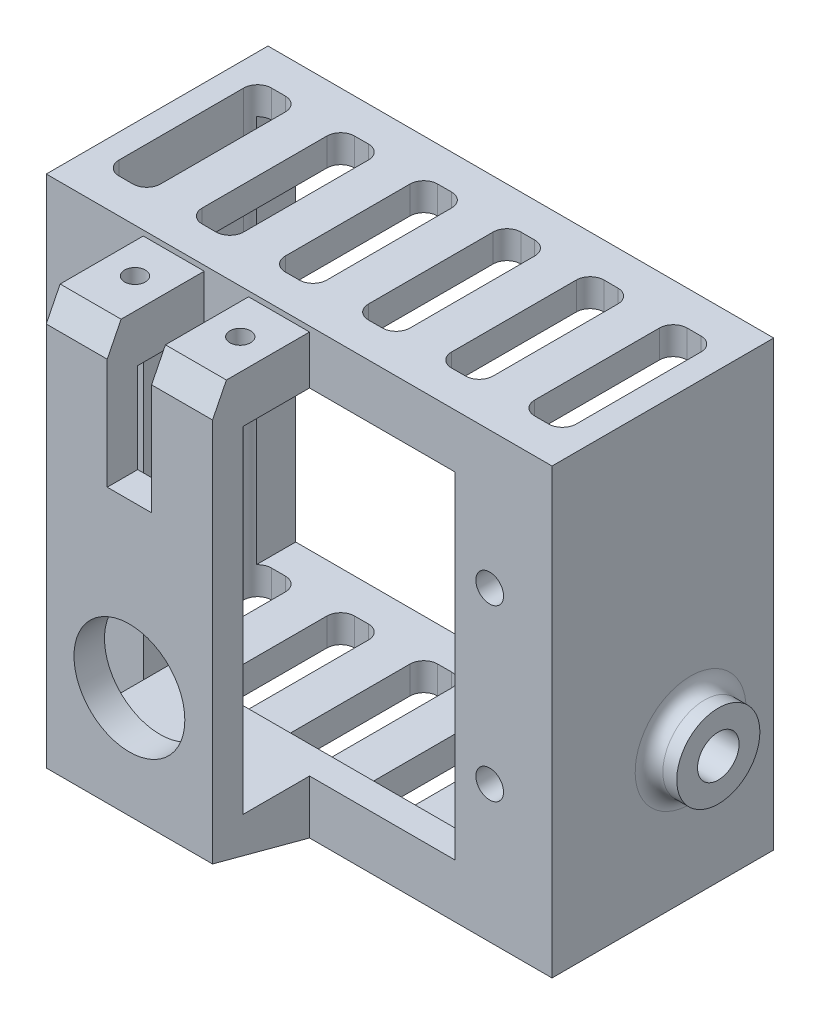
SolidWorks part; units mm, degrees
ref_plane "前视基准面" through (0, 0, 0) normal (0, 0, 1) x (1, 0, 0)
ref_plane "上视基准面" through (0, 0, 0) normal (0, 1, 0) x (1, 0, 0)
ref_plane "右视基准面" through (0, 0, 0) normal (1, 0, 0) x (0, 0, -1)
sketch "草图1" plane through (0, 0, 0) normal (0, 0, 1) x (1, 0, 0)
  line L0 (0, 16.832) -> (0, -37.7985) construction
  line L1 (-34.0238, 0) -> (58.9478, 0) construction
  line L2 (-19, 0) -> (-19, 8.7719) construction
  line L3 (8.5, 0) -> (8.5, 10.2817) construction
  line L4 (-19, 6) -> (8.5, 6) construction
  line L5 (-5.25, 8.9788) -> (-5.25, 6) construction
  line L6 (-16.5, 6) -> (-16.5, -18.25)
  line L7 (6, 6) -> (6, -18.25)
  line L9 (-16.5, 6) -> (6, 6)
  line L10 (-16.5, -18.25) -> (6, -18.25)
  line L11 (-21.5, 9.875) -> (11, 9.875)
  line L12 (11, 9.875) -> (11, -22.125)
  line L13 (-21.5, 9.875) -> (-21.5, -22.125)
  line L14 (-21.5, -22.125) -> (11, -22.125)
  line L15 (-16.5, -6.125) -> (6, -6.125) construction
  circle A0 centre (-19, 0) radius 1
  circle A1 centre (8.5, 0) radius 1
  circle A2 centre (-19, -12.25) radius 1
  circle A3 centre (8.5, -12.25) radius 1
  dimension "D3" = 2
  dimension "D1" = 6
  dimension "D2" = 24.25
  dimension "D4" = 16
  dimension "D5" = 16
  dimension "D6" = 8.5
  dimension "D7" = 16.5
  dimension "D8" = 5
  dimension "D9" = 5
  dimension "D10" = 6
extrude "凸台-拉伸1" add sketch "草图1" along normal blind 2
ref_plane "基准面4" through (0, 0, 9) normal (0, 0, 1) x (1, 0, 0)
sketch "草图2" plane through (0, 0, 9) normal (0, 0, 1) x (1, 0, 0)
  line L0 (-16.5, -6.125) -> (6, -6.125) construction
  line L1 (-16.5, 6) -> (-16.5, -18.25) construction
  line L2 (6, -18.25) -> (6, 6) construction
  line L3 (-5.25, 6) -> (-5.25, -18.25) construction
  line L4 (6, 6) -> (-16.5, 6) construction
  line L5 (-16.5, -18.25) -> (6, -18.25) construction
  line L6 (-19, -12.25) -> (8.5, -12.25) construction
  line L7 (-19, 0) -> (8.5, 0) construction
  line L9 (-4.5, -6.25) -> (-16.5, -6.25)
  line L10 (-4.5, -6.25) -> (-4.5, -18.25)
  line L11 (-4.5, -18.25) -> (-16.5, -18.25)
  line L12 (-16.5, -6.25) -> (-16.5, -18.25)
  line L13 (-4.5, -6.25) -> (-16.5, -18.25) construction
  line L14 (-4.5, -18.25) -> (-16.5, -6.25) construction
  circle A0 centre (-10.5, -12.25) radius 6 construction
  circle A2 centre (-10.5, -12.25) radius 4
  dimension "D2" = 12
  dimension "D3" = 8
  dimension "D1" = 19
  dimension "D4" = 12
extrude "凸台-拉伸2" add sketch "草图2" against normal blind 2.2 separate body
sketch "草图3" plane through (-16.5, 0, 0) normal (-1, 0, 0) x (0, 0, 1)
  line L0 (9, -18.25) -> (2, -18.25)
  line L1 (2, -18.25) -> (2, -22.125)
  line L2 (2, 9.875) -> (2, -22.125) construction
  line L3 (2, -22.125) -> (0, -22.125) construction
  line L4 (2, -22.125) -> (9, -20.25)
  line L5 (9, -20.25) -> (9, -18.25)
  dimension "D1" = 2
extrude "凸台-拉伸3" add sketch "草图3" against normal up to surface (12 mm away) up to face at (-4.5, -12.25, 7.9)
sketch "草图4" plane through (-16.5, 0, 0) normal (-1, 0, 0) x (0, 0, 1)
  line L0 (6.8, -6.25) -> (9, -6.25)
  line L1 (9, -6.25) -> (9, 9.5)
  line L2 (9, 9.5) -> (2, 9.5)
  line L3 (6.8, -6.25) -> (6.8, 6)
  line L4 (6.8, 6) -> (2, 6)
  line L5 (2, 6) -> (2, 9.5)
  dimension "D1" = 3.5
extrude "凸台-拉伸4" add sketch "草图4" against normal up to surface (12 mm away) up to face at (-4.5, -15.2292, 5.9333)
sketch "草图5" plane through (0, 0, 0) normal (0, 0, -1) x (-1, 0, 0)
  line L0 (-11, 9.875) -> (21.5, 9.875)
  line L1 (21.5, 9.875) -> (21.5, 7.875)
  line L2 (21.5, 9.875) -> (21.5, -22.125) construction
  line L3 (21.5, 7.875) -> (-11, 7.875)
  line L4 (-11, -22.125) -> (-11, 9.875) construction
  line L5 (-11, 7.875) -> (-11, 9.875)
  line L6 (-6, -6.125) -> (16.5, -6.125) construction
  line L7 (-6, -18.25) -> (-6, 6) construction
  line L8 (16.5, 6) -> (16.5, -18.25) construction
  line L9 (-11, -20.125) -> (-11, -22.125)
  line L10 (21.5, -20.125) -> (-11, -20.125)
  line L11 (21.5, -22.125) -> (21.5, -20.125)
  line L12 (-11, -22.125) -> (21.5, -22.125)
  dimension "D1" = 2
extrude "凸台-拉伸5" add sketch "草图5" along normal blind 14
sketch "草图7" plane through (0, 0, 2) normal (0, 0, 1) x (1, 0, 0)
  line L0 (-5.25, 9.875) -> (-5.25, 15.8183) construction
  line L1 (11, 9.875) -> (-21.5, 9.875) construction
  line L2 (-21.5, 9.875) -> (-23.5, 9.875)
  line L3 (-23.5, -22.125) -> (-21.5, -22.125)
  line L4 (-21.5, -22.125) -> (-21.5, 9.875)
  line L5 (-23.5, 9.875) -> (-23.5, -22.125)
  line L6 (13, 9.875) -> (13, -22.125)
  line L7 (11, -22.125) -> (11, 9.875)
  line L8 (13, -22.125) -> (11, -22.125)
  line L9 (11, 9.875) -> (13, 9.875)
  dimension "D1" = 2
extrude "凸台-拉伸6" add sketch "草图7" against normal blind 16
ref_plane "基准面5" through (0, 0, -8) normal (0, 0, -1) x (-1, 0, 0)
sketch "草图8" plane through (0, 0, -8) normal (0, 0, -1) x (-1, 0, 0)
  line L0 (-6, -6.125) -> (2.8741, -6.125) construction
  line L1 (-6, -18.25) -> (-6, 6) construction
  line L2 (19, -12.25) -> (-19.2584, -12.25) construction
  line L3 (19, -12.25) -> (28.1936, -12.25) construction
sketch "草图9" plane through (-23.5, 0, 0) normal (1, 0, 0) x (0, 0, -1)
  line L0 (8, -17.6) -> (8, 17.6) construction
  circle A0 centre (8, -12.25) radius 3.625
  dimension "D1" = 7.25
extrude "切除-拉伸1" cut sketch "草图9" along normal blind 1
sketch "草图10" plane through (-22.5, 0, 0) normal (-1, 0, 0) x (0, 0, 1)
  circle A0 centre (-8, -12.25) radius 2.25
  dimension "D1" = 4.5
extrude "切除-拉伸2" cut sketch "草图10" against normal blind 1
sketch "草图11" plane through (-23.5, 0, 0) normal (1, 0, 0) x (0, 0, -1)
  circle A0 centre (8, -12.25) radius 5
  circle A1 centre (8, -12.25) radius 3.625 construction
  circle A2 centre (8, -12.25) radius 3.625
  dimension "D1" = 10
extrude "凸台-拉伸7" add sketch "草图11" against normal blind 2
fillet "圆角1" radius 1 1 edges at (-23.5, -17.25, -8)
sketch "草图12" plane through (13, 0, 0) normal (-1, 0, 0) x (0, 0, 1)
  circle A0 centre (-8, -12.25) radius 1.5
  circle A1 centre (-8, -12.25) radius 3
  dimension "D1" = 3
  dimension "D2" = 6
extrude "凸台-拉伸8" add sketch "草图12" against normal blind 2
fillet "圆角2" radius 1 1 edges at (13, -9.25, -8)
sketch "草图13" plane through (13, 0, 0) normal (-1, 0, 0) x (0, 0, 1)
  circle A0 centre (-8, -12.25) radius 1.5 construction
  circle A1 centre (-8, -12.25) radius 1.5
extrude "切除-拉伸3" cut sketch "草图13" along normal blind 2
sketch "草图14" [suppressed] plane through (13, 0, 0) normal (1, 0, 0) x (0, 0, -1)
  circle A0 centre (8, -12.25) radius 3.625
  dimension "D1" = 7.25
extrude "切除-拉伸4" [suppressed] cut sketch "草图14" against normal blind 1
sketch "草图15" [suppressed] plane through (12, 0, 0) normal (1, 0, 0) x (0, 0, -1)
  circle A0 centre (8, -12.25) radius 2.25
  dimension "D1" = 4.5
extrude "切除-拉伸5" [suppressed] cut sketch "草图15" against normal blind 1
sketch "草图16" [suppressed] plane through (13, 0, 0) normal (1, 0, 0) x (0, 0, -1)
  circle A0 centre (8, -12.25) radius 5
  circle A1 centre (8, -12.25) radius 3.625 construction
  circle A2 centre (8, -12.25) radius 3.625
  dimension "D1" = 10
extrude "凸台-拉伸9" [suppressed] add sketch "草图16" along normal blind 2
fillet "圆角3" [suppressed] radius 1
sketch "草图17" [suppressed] plane through (-23.5, 0, 0) normal (-1, 0, 0) x (0, 0, 1)
  circle A0 centre (-8, -12.25) radius 1.5
  circle A1 centre (-8, -12.25) radius 3
  dimension "D1" = 3
  dimension "D2" = 6
extrude "凸台-拉伸10" [suppressed] add sketch "草图17" along normal blind 2
fillet "圆角4" [suppressed] radius 1
sketch "草图18" [suppressed] plane through (-23.5, 0, 0) normal (-1, 0, 0) x (0, 0, 1)
  circle A3 centre (-8, -12.25) radius 1.5
  circle A4 centre (-8, -12.25) radius 1.5
  dimension "D1" = 0
extrude "切除-拉伸6" [suppressed] cut sketch "草图18" against normal blind 2
sketch "草图19" plane through (0, 9.5, 0) normal (0, 1, 0) x (1, 0, 0)
  line L0 (-10.5, -9) -> (-10.5, -2) construction
  line L1 (-4.5, -9) -> (-16.5, -9) construction
  line L2 (13, -2) -> (-23.5, -2) construction
  line L3 (-12.1005, -2) -> (-8.8995, -2)
  line L4 (-4.5, -2) -> (-16.5, -2) construction
  line L5 (-8.8995, -2) -> (-8.8995, -9)
  line L6 (-8.8995, -9) -> (-12.1005, -9)
  line L7 (-12.1005, -2) -> (-12.1005, -9)
  dimension "D1" = 3.201
extrude "切除-拉伸7" cut sketch "草图19" against normal blind 10
sketch "草图20" plane through (0, 9.875, 0) normal (0, 1, 0) x (1, 0, 0)
  line L0 (-5.25, 14) -> (-5.25, -2) construction
  line L1 (-23.5, 14) -> (13, 14) construction
  line L2 (13, -2) -> (-23.5, -2) construction
  line L3 (-6.75, 10.5) -> (-6.75, 1.5)
  line L4 (-7.75, 0.5) -> (-8.75, 0.5)
  line L5 (-9.75, 1.5) -> (-9.75, 10.5)
  line L6 (-8.75, 11.5) -> (-7.75, 11.5)
  line L7 (8.25, 10.5) -> (8.25, 1.5)
  line L8 (-14.75, 11.5) -> (-13.75, 11.5)
  line L9 (-15.75, 10.5) -> (-15.75, 1.5)
  line L10 (-14.75, 0.5) -> (-13.75, 0.5)
  line L11 (-12.75, 10.5) -> (-12.75, 1.5)
  line L12 (-20.75, 11.5) -> (-19.75, 11.5)
  line L13 (-21.75, 10.5) -> (-21.75, 1.5)
  line L14 (-20.75, 0.5) -> (-19.75, 0.5)
  line L15 (-18.75, 10.5) -> (-18.75, 1.5)
  line L16 (10.25, 0.5) -> (9.25, 0.5)
  line L17 (11.25, 10.5) -> (11.25, 1.5)
  line L18 (10.25, 11.5) -> (9.25, 11.5)
  line L19 (2.25, 10.5) -> (2.25, 1.5)
  line L20 (4.25, 0.5) -> (3.25, 0.5)
  line L21 (5.25, 10.5) -> (5.25, 1.5)
  line L22 (4.25, 11.5) -> (3.25, 11.5)
  line L23 (-1.75, 11.5) -> (-2.75, 11.5)
  line L24 (-0.75, 1.5) -> (-0.75, 10.5)
  line L25 (-2.75, 0.5) -> (-1.75, 0.5)
  line L26 (-3.75, 10.5) -> (-3.75, 1.5)
  arc A0 (4.25, 0.5) -> (5.25, 1.5) centre (4.25, 1.5) ccw
  arc A1 (2.25, 1.5) -> (3.25, 0.5) centre (3.25, 1.5) ccw
  arc A2 (-0.75, 1.5) -> (-1.75, 0.5) centre (-1.75, 1.5) cw
  arc A3 (-2.75, 0.5) -> (-3.75, 1.5) centre (-2.75, 1.5) cw
  arc A4 (-6.75, 1.5) -> (-7.75, 0.5) centre (-7.75, 1.5) cw
  arc A5 (-8.75, 0.5) -> (-9.75, 1.5) centre (-8.75, 1.5) cw
  arc A6 (-13.75, 0.5) -> (-12.75, 1.5) centre (-13.75, 1.5) ccw
  arc A7 (-15.75, 1.5) -> (-14.75, 0.5) centre (-14.75, 1.5) ccw
  arc A8 (-19.75, 0.5) -> (-18.75, 1.5) centre (-19.75, 1.5) ccw
  arc A9 (-21.75, 1.5) -> (-20.75, 0.5) centre (-20.75, 1.5) ccw
  arc A10 (8.25, 1.5) -> (9.25, 0.5) centre (9.25, 1.5) ccw
  arc A11 (10.25, 0.5) -> (11.25, 1.5) centre (10.25, 1.5) ccw
  arc A12 (8.25, 10.5) -> (9.25, 11.5) centre (9.25, 10.5) cw
  arc A13 (11.25, 10.5) -> (10.25, 11.5) centre (10.25, 10.5) ccw
  arc A14 (5.25, 10.5) -> (4.25, 11.5) centre (4.25, 10.5) ccw
  arc A15 (2.25, 10.5) -> (3.25, 11.5) centre (3.25, 10.5) cw
  arc A16 (-1.75, 11.5) -> (-0.75, 10.5) centre (-1.75, 10.5) cw
  arc A17 (-2.75, 11.5) -> (-3.75, 10.5) centre (-2.75, 10.5) ccw
  arc A18 (-6.75, 10.5) -> (-7.75, 11.5) centre (-7.75, 10.5) ccw
  arc A19 (-9.75, 10.5) -> (-8.75, 11.5) centre (-8.75, 10.5) cw
  arc A20 (-13.75, 11.5) -> (-12.75, 10.5) centre (-13.75, 10.5) cw
  arc A21 (-14.75, 11.5) -> (-15.75, 10.5) centre (-14.75, 10.5) ccw
  arc A22 (-19.75, 11.5) -> (-18.75, 10.5) centre (-19.75, 10.5) cw
  arc A23 (-20.75, 11.5) -> (-21.75, 10.5) centre (-20.75, 10.5) ccw
  point P30 (9.75, 0.5)
  point P33 (5.25, 0.5)
  point P36 (2.25, 0.5)
  point P39 (-0.75, 0.5)
  point P42 (-3.75, 0.5)
  point P45 (-6.75, 0.5)
  point P48 (-9.75, 0.5)
  point P51 (-12.75, 0.5)
  point P54 (-15.75, 0.5)
  point P57 (-18.75, 0.5)
  point P60 (-21.75, 0.5)
  point P63 (8.25, 0.5)
  point P66 (11.25, 0.5)
  point P69 (8.25, 11.5)
  point P72 (11.25, 11.5)
  point P75 (5.25, 11.5)
  point P78 (2.25, 11.5)
  point P81 (-0.75, 11.5)
  point P84 (-3.75, 11.5)
  point P87 (-6.75, 11.5)
  point P90 (-9.75, 11.5)
  point P93 (-12.75, 11.5)
  point P96 (-15.75, 11.5)
  point P99 (-18.75, 11.5)
  point P102 (-21.75, 11.5)
  dimension "D9" = 1
  dimension "D1" = 3
  dimension "D2" = 3
  dimension "D3" = 3
  dimension "D4" = 3
  dimension "D5" = 3
  dimension "D6" = 3
  dimension "D7" = 2.5
  dimension "D8" = 2.5
extrude "切除-拉伸8" cut sketch "草图20" against normal blind 42
sketch "草图22" plane through (0, 9.5, 0) normal (0, 1, 0) x (1, 0, 0)
  line L0 (-10.5, -2) -> (-10.5, -9) construction
  line L1 (13, -2) -> (-23.5, -2) construction
  line L2 (-12.1005, -9) -> (-8.8995, -9) construction
  line L3 (-4.5, -2) -> (-8.8995, -2) construction
  circle A0 centre (-6.7, -4.8) radius 0.75
  circle A1 centre (-14.3, -4.8) radius 0.75
  dimension "D2" = 2.8
  dimension "D3" = 1.5
  dimension "D1" = 3.8
extrude "切除-拉伸9" cut sketch "草图22" against normal blind 5
chamfer "倒角1" distance 1 distance2 2 2 edges at (-6.6998, 9.5, 9) (-14.3002, 9.5, 9) first distance on face at (-6.7, 9.5, 5.55) first distance on face at (-14.3, 9.5, 4.05)
